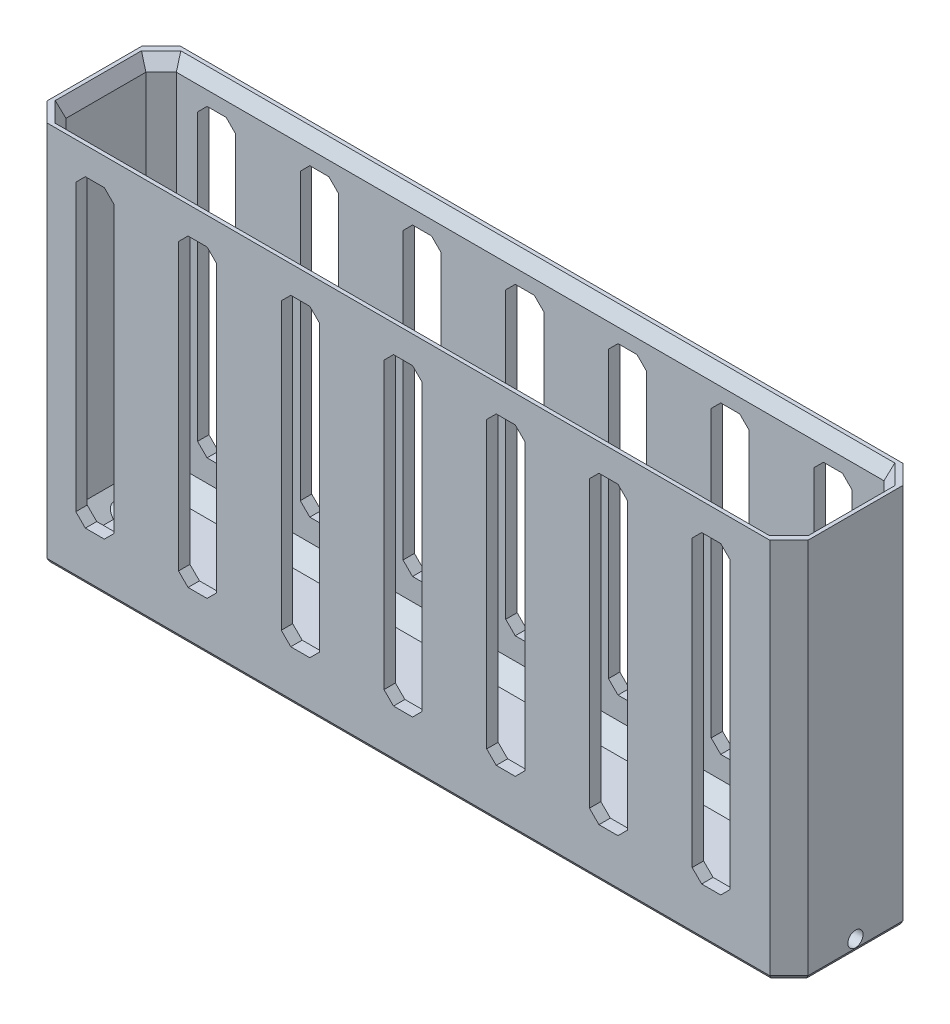
SolidWorks part; units mm, degrees
ref_plane "Front Plane" through (0, 0, 0) normal (0, 0, 1) x (1, 0, 0)
ref_plane "Top Plane" through (0, 0, 0) normal (0, 1, 0) x (1, 0, 0)
ref_plane "Right Plane" through (0, 0, 0) normal (1, 0, 0) x (0, 0, -1)
sketch "Sketch1" plane through (0, 0, 0) normal (0, 1, 0) x (1, 0, 0)
  line L0 (-97, 16.975) -> (-97, 14.5) construction
  line L1 (100, -17.5) -> (-100, -17.5)
  line L2 (100, -17.5) -> (100, 17.5)
  line L3 (100, 17.5) -> (-100, 17.5)
  line L4 (-100, -17.5) -> (-100, 17.5)
  line L5 (100, -17.5) -> (-82.8571, 14.5) construction
  line L6 (100, 17.5) -> (-100, -17.5) construction
  line L7 (-100, 17.5) -> (-97, 17.5)
  line L8 (-100, 17.5) -> (-100, 14.5)
  line L9 (-100, 14.5) -> (-97, 14.5) construction
  line L10 (-97, 17.5) -> (-97, 16.975) construction
  line L11 (97, -14.5) -> (-97, -14.5)
  line L12 (97, -14.5) -> (97, 14.5)
  line L13 (97, 14.5) -> (-97, 14.5)
  line L14 (-97, -14.5) -> (-97, 14.5)
  line L15 (97, -14.5) -> (-97, 14.5) construction
  line L16 (97, 14.5) -> (-97, -14.5) construction
  line L17 (-82.8571, 14.5) -> (-97, 16.975) construction
  line L18 (-97, 16.975) -> (-100, 17.5) construction
  point P0 (0, 0)
  point P9 (0, 0)
extrude "Boss-Extrude1" add sketch "Sketch1" along normal blind 100 contours L4 L1 L2 L3 L11 L14 L13 L12 region at (0, 0, 15.4696)
extrude "Boss-Extrude2" add sketch "Sketch1<3>" along normal blind 3 contours L14 L11 L12 L13 region at (0, 0, 0)
sketch "Sketch1<3>" plane through (0, 0, 0) normal (0, 1, 0) x (1, 0, 0) same geometry as "Sketch1"
chamfer "Chamfer1" distance 4 angle 45 8 edges at (0, 3, -14.5) (97, 51.5, -14.5) (97, 3, 0) (97, 51.5, 14.5) (0, 3, 14.5) (-97, 51.5, 14.5) (-97, 3, 0) (-97, 51.5, -14.5)
chamfer "Chamfer2" distance 5 angle 45 4 edges at (100, 50, -17.5) (100, 50, 17.5) (-100, 50, 17.5) (-100, 50, -17.5)
chamfer "Chamfer3" distance 2 angle 60 8 edges at (95, 100, 12.5) (97, 100, 0) (95, 100, -12.5) (0, 100, 14.5) (-95, 100, 12.5) (-97, 100, 0) (-95, 100, -12.5) (0, 100, -14.5) first distance on face at (0, 100, 0)
sketch "Sketch2" plane through (100, 0, 0) normal (1, 0, 0) x (0, 0, -1)
  line L0 (0, 0) -> (0, 1) construction
  line L1 (-12.5, 0) -> (12.5, 0) construction
  line L2 (0, 1) -> (0, 3) construction
  circle A0 centre (0, 3) radius 2
extrude "Cut-Extrude1" cut sketch "Sketch2" against normal blind 10
mirror "Mirror1" about plane through (0, 0, 0) normal (1, 0, 0) of "Cut-Extrude1"
chamfer "Chamfer4" distance 0.5 angle 60 8 edges at (-97.5, 0, -15) (-100, 0, 0) (-97.5, 0, 15) (0, 0, 17.5) (97.5, 0, 15) (100, 0, 0) (97.5, 0, -15) (0, 0, -17.5) first distance on face at (0, 0, 0)
sketch "Sketch3" plane through (0, 0, 17.5) normal (0, 0, 1) x (1, 0, 0)
  line L0 (-87.4212, 90.2933) -> (-84.9212, 92.7933)
  line L11 (-84.9212, 92.7933) -> (-79.9212, 92.7933)
  line L12 (-87.4212, 90.2933) -> (-87.4212, 15.2933)
  line L13 (-84.9212, 12.7933) -> (-79.9212, 12.7933)
  line L14 (-77.4212, 90.2933) -> (-77.4212, 15.2933)
  line L15 (-79.9212, 92.7933) -> (-77.4212, 90.2933)
  line L16 (-87.4212, 15.2933) -> (-84.9212, 12.7933)
  line L17 (-79.9212, 12.7933) -> (-77.4212, 15.2933)
  point P0 (-87.4212, 92.7933)
  point P1 (-77.4212, 12.7933)
  point P2 (-87.4212, 12.7933)
  point P3 (-77.4212, 92.7933)
  point P8 (0, 0)
extrude "Cut-Extrude2" cut sketch "Sketch3" against normal up to surface (35 mm away) up to face at (0, 50.433, -17.5)
pattern_linear "LPattern2" count 7 spacing 27 along (1, 0, 0) of "Cut-Extrude2"
